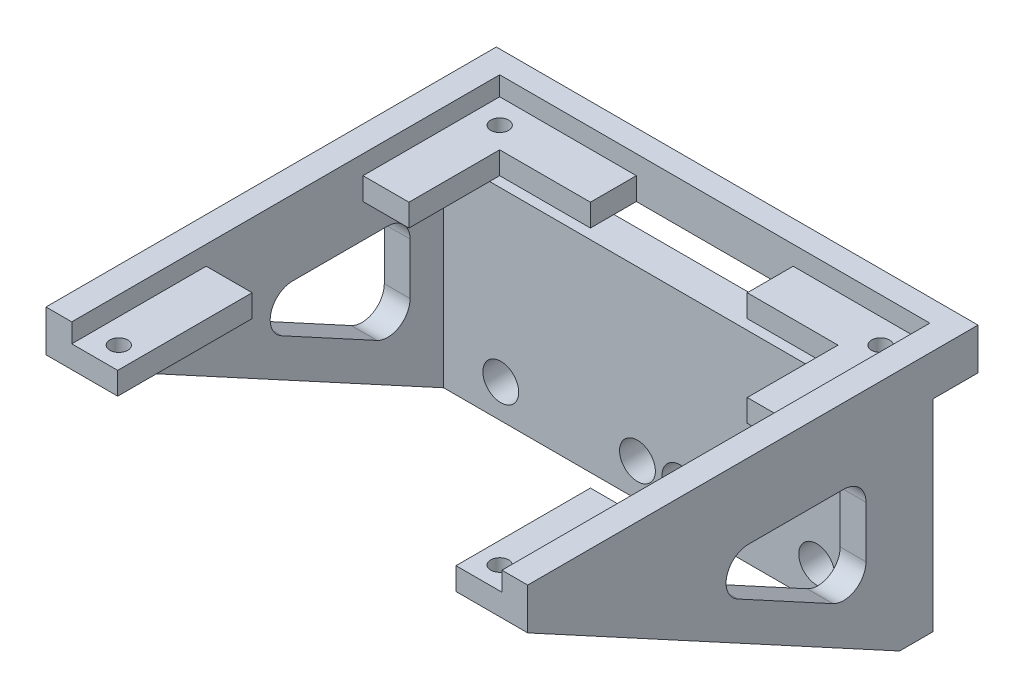
SolidWorks part; units mm, degrees
ref_plane "前视基准面" through (0, 0, 0) normal (0, 0, 1) x (1, 0, 0)
ref_plane "上视基准面" through (0, 0, 0) normal (0, 1, 0) x (1, 0, 0)
ref_plane "右视基准面" through (0, 0, 0) normal (1, 0, 0) x (0, 0, -1)
sketch "Sketch1" plane through (0, 0, 0) normal (0, 1, 0) x (1, 0, 0)
  line L1 (-21.5, -21.5) -> (21.5, -21.5)
  line L2 (-21.5, -21.5) -> (-21.5, 21.5)
  line L3 (-21.5, 21.5) -> (21.5, 21.5)
  line L4 (21.5, -21.5) -> (21.5, 21.5)
  line L5 (-21.5, -21.5) -> (21.5, 21.5) construction
  line L6 (-21.5, 21.5) -> (21.5, -21.5) construction
  point P0 (0, 0)
  dimension "D1" = 43
  dimension "D2" = 43
extrude "Boss-Extrude1" add sketch "Sketch1" along normal blind 24
sketch "Sketch2" plane through (0, 24, 0) normal (0, 1, 0) x (1, 0, 0)
  line L0 (0, 0) -> (0, -21.5) construction
  line L1 (-21.5, -21.5) -> (21.5, -21.5) construction
  line L3 (-19.2, -21.5) -> (19.2, -21.5)
  line L4 (-19.2, -21.5) -> (-19.2, 16.7)
  line L5 (-19.2, 16.7) -> (19.2, 16.7)
  line L6 (19.2, -21.5) -> (19.2, 16.7)
  dimension "D1" = 38.4
  dimension "D2" = 19.2
  dimension "D3" = 38.2
extrude "Cut-Extrude1" cut sketch "Sketch2" against normal blind 1.7
sketch "Sketch3" plane through (0, 22.3, 0) normal (0, 1, 0) x (1, 0, 0)
  line L0 (0, -21.5) -> (0, -2.5) construction
  line L1 (-19.2, -21.5) -> (19.2, -21.5) construction
  line L3 (-17, -19.5) -> (17, -19.5)
  line L4 (-17, -19.5) -> (-17, 14.5)
  line L5 (-17, 14.5) -> (17, 14.5)
  line L6 (17, -19.5) -> (17, 14.5)
  line L7 (-17, -19.5) -> (17, 14.5) construction
  line L8 (-17, 14.5) -> (17, -19.5) construction
  dimension "D1" = 19
  dimension "D2" = 34
  dimension "D3" = 34
hole_wizard "Ø1.6 (1.6) Diameter Hole1" positions "3DSketch1" profile "Sketch4" hole size "Ø1.6" standard "ANSI Metric" end condition through all
sketch3d "3DSketch1"
  point P0 (-17, 22.3, -14.5)
  point P3 (17, 22.3, -14.5)
  point P6 (17, 22.3, 19.5)
  point P9 (-17, 22.3, 19.5)
sketch "Sketch4" plane through (-17, 22.3, -14.5) normal (1, 0, 0) x (0, 0, 1)
  line L0 (0, 0) -> (0, 22.3)
  line L1 (0, 22.3) -> (0.8, 22.3)
  line L2 (0.8, 22.3) -> (0.8, 0)
  line L5 (0.8, 0) -> (0, 0)
  line L11 (0, -6.35) -> (0, 107.95) construction
  dimension "Thru Hole Dia." = 1.6
  dimension "Thru Hole Depth" = 22.3
sketch "Sketch5" plane through (0, 22.3, 0) normal (0, 1, 0) x (1, 0, 0)
  line L0 (-15.1, -21.5) -> (-15.1, 12.6)
  line L1 (-19.2, -21.5) -> (19.2, -21.5) construction
  line L2 (-15.1, 12.6) -> (15.1, 12.6)
  line L3 (15.1, 12.6) -> (15.1, -21.5)
  line L4 (15.1, -21.5) -> (-15.1, -21.5)
  line L5 (0, -21.5) -> (0, -2.5) construction
  dimension "D1" = 15.1
  dimension "D2" = 15.1
  dimension "D3" = 15.1
extrude "Cut-Extrude2" cut sketch "Sketch5" against normal blind 2
sketch "Sketch6" plane through (0, 22.3, 0) normal (0, 1, 0) x (1, 0, 0)
  line L0 (0, 0) -> (0, 16.7) construction
  line L1 (19.2, 16.7) -> (-19.2, 16.7) construction
  line L3 (-7, 16.7) -> (7, 16.7)
  line L4 (-7, 16.7) -> (-7, 4.7)
  line L5 (-7, 4.7) -> (7, 4.7)
  line L6 (7, 16.7) -> (7, 4.7)
  dimension "D1" = 12
  dimension "D2" = 7
  dimension "D3" = 7
extrude "Cut-Extrude3" cut sketch "Sketch6" against normal through all
sketch "Sketch7" plane through (0, 20.3, 0) normal (0, 1, 0) x (1, 0, 0)
  line L0 (-15.1, -21.5) -> (15.1, -21.5) construction
  line L1 (-14.45, -49.4913) -> (14.45, -49.4913)
  line L2 (-14.45, -49.4913) -> (-14.45, 6.4913)
  line L3 (-14.45, 6.4913) -> (14.45, 6.4913)
  line L4 (14.45, -49.4913) -> (14.45, 6.4913)
  line L5 (-14.45, -49.4913) -> (14.45, 6.4913) construction
  line L6 (-14.45, 6.4913) -> (14.45, -49.4913) construction
  point P0 (0, -21.5)
  dimension "D1" = 28.9
extrude "Cut-Extrude4" cut sketch "Sketch7" against normal through all
sketch "Sketch8" plane through (0, 0, 21.5) normal (0, 0, 1) x (1, 0, 0)
  line L1 (-14.45, 20.3) -> (-21.5, 20.3)
  line L2 (-14.45, 20.3) -> (-14.45, 0)
  line L3 (-14.45, 0) -> (-21.5, 0)
  line L4 (-21.5, 20.3) -> (-21.5, 0)
extrude "Boss-Extrude2" add sketch "Sketch8" along normal blind 8.2
mirror "Mirror1" about plane through (0, 0, 0) normal (1, 0, 0) of "Boss-Extrude2"
sketch "Sketch9" plane through (-14.45, 0, 0) normal (1, 0, 0) x (0, 0, -1)
  line L0 (6.4913, 0) -> (6.4913, 20.3) construction
  line L1 (-29.7, 0) -> (6.4913, 0)
  line L2 (-29.7, 0) -> (-29.7, 11.8)
  line L3 (-29.7, 11.8) -> (6.4913, 11.8)
  line L4 (6.4913, 0) -> (6.4913, 11.8)
  line L5 (6.4913, 20.3) -> (-29.7, 20.3) construction
  dimension "D1" = 8.5
extrude "Cut-Extrude5" cut sketch "Sketch9" against normal blind 4.1
mirror "Mirror2" about plane through (0, 0, 0) normal (1, 0, 0) of "Cut-Extrude5"
sketch "Sketch10" plane through (-21.5, 0, 0) normal (-1, 0, 0) x (0, 0, 1)
  line L1 (6.7, 5.05) -> (18.7, 5.05)
  line L5 (29.7, 20.3) -> (21.5, 20.3) construction
  dimension "D2" = 12
  dimension "D3" = 15.25
hole_wizard "Ø2.9 (2.9) Diameter Hole1" positions "Sketch11" profile "Sketch12" hole size "Ø2.9" standard "ANSI Metric" end condition through all
sketch "Sketch11" plane through (-21.5, 0, 0) normal (-1, 0, 0) x (0, 0, 1)
  point P0 (6.7, 5.05)
  point P3 (18.7, 5.05)
sketch "Sketch12" plane through (-21.5, 5.05, 6.7) normal (0, 1, 0) x (0, 0, 1)
  line L0 (0, 0) -> (0, 43)
  line L1 (0, 43) -> (1.45, 43)
  line L2 (1.45, 43) -> (1.45, 0)
  line L5 (1.45, 0) -> (0, 0)
  line L11 (0, -6.35) -> (0, 107.95) construction
  dimension "Thru Hole Dia." = 2.9
  dimension "Thru Hole Depth" = 43
sketch "Sketch13" plane through (0, 0, 0) normal (0, -1, 0) x (1, 0, 0)
  line L0 (21.5, -21.5) -> (-21.5, -21.5) construction
  line L1 (22.5, -36.5087) -> (-22.5, -36.5087)
  line L2 (22.5, -36.5087) -> (22.5, -6.4913)
  line L3 (22.5, -6.4913) -> (-22.5, -6.4913)
  line L4 (-22.5, -36.5087) -> (-22.5, -6.4913)
  line L5 (22.5, -36.5087) -> (-22.5, -6.4913) construction
  line L6 (22.5, -6.4913) -> (-22.5, -36.5087) construction
  line L7 (-7, -6.4913) -> (-18.55, -6.4913) construction
  point P0 (0, -21.5)
  dimension "D1" = 45
extrude "Cut-Extrude6" cut sketch "Sketch13" against normal blind 11.8
sketch "Sketch14" plane through (0, 24, 0) normal (0, 1, 0) x (1, 0, 0)
  circle A0 centre (-19.2, 16.7) radius 0.5
  dimension "D1" = 1
sketch "草图1" plane through (0, 0, 29.7) normal (0, 0, 1) x (1, 0, 0)
  line L0 (-7, 20.3) -> (-14.45, 20.3) construction
  line L1 (-28.0658, 20.3) -> (26.3141, 20.3)
  line L2 (-28.0658, 20.3) -> (-28.0658, -5.4429)
  line L3 (-28.0658, -5.4429) -> (26.3141, -5.4429)
  line L4 (26.3141, 20.3) -> (26.3141, -5.4429)
extrude "切除-拉伸1" cut sketch "草图1" against normal through all
sketch "草图2" plane through (0, 24, 0) normal (0, 1, 0) x (1, 0, 0)
  line L1 (-23.9155, 26.9484) -> (27.254, 26.9484)
  line L2 (-23.9155, 26.9484) -> (-23.9155, 18.7)
  line L3 (-23.9155, 18.7) -> (27.254, 18.7)
  line L4 (27.254, 26.9484) -> (27.254, 18.7)
  line L6 (-7, 16.7) -> (-19.2, 16.7) construction
  dimension "D1" = 2
extrude "切除-拉伸4" cut sketch "草图2" against normal blind 10
sketch "草图3" plane through (0, 20.3, 0) normal (0, -1, 0) x (1, 0, 0)
  line L0 (17, 19.5) -> (17, -14.5) construction
  line L1 (-17, 19.5) -> (-17, -14.5) construction
  line L2 (-19.2, 9.5) -> (19.2, 9.5)
  line L3 (-19.2, 9.5) -> (-19.2, -4.5)
  line L4 (-19.2, -4.5) -> (19.2, -4.5)
  line L5 (19.2, 9.5) -> (19.2, -4.5)
  point P12 (19.5094, 9.5)
  point P13 (17, -4.5)
  point P14 (0, 0)
  point P15 (19.5094, -4.5)
  dimension "D1" = 10
  dimension "D2" = 10
  dimension "D3" = 2.2
  dimension "D4" = 2.2
extrude "切除-拉伸5" cut sketch "草图3" against normal through all
sketch "草图4" plane through (0, 20.3, 0) normal (0, -1, 0) x (1, 0, 0)
  line L0 (-21.5, -18.7) -> (-21.5, 21.5) construction
  line L1 (-21.5, -11.7) -> (21.5, -11.7)
  line L2 (-21.5, -11.7) -> (-21.5, -14.7)
  line L3 (-21.5, -14.7) -> (21.5, -14.7)
  line L4 (21.5, -11.7) -> (21.5, -14.7)
  line L5 (21.5, 21.5) -> (21.5, -18.7) construction
  line L6 (-21.5, -18.7) -> (21.5, -18.7) construction
  dimension "D1" = 3
  dimension "D2" = 4
extrude "凸台-拉伸1" add sketch "草图4" along normal blind 18
sketch "草图5" plane through (0, 0, -14.7) normal (0, 0, -1) x (-1, 0, 0)
  line L0 (7, 20.3) -> (-7, 20.3) construction
  line L1 (-21.5, 2.3) -> (-21.5, 20.3) construction
  line L2 (-7, 20.3) -> (-16.2254, 20.3) construction
  line L3 (21.5, 2.3) -> (21.5, 20.3) construction
  circle A0 centre (0, 14.3) radius 2.75
  circle A1 centre (-1.9, 5.3) radius 1.6
  circle A2 centre (14.1, 5.3) radius 1.6
  dimension "D3" = 5.5
  dimension "D4" = 3.2
  dimension "D7" = 16
  dimension "D1" = 6
  dimension "D2" = 21.5
  dimension "D5" = 15
  dimension "D6" = 7.4
extrude "切除-拉伸6" cut sketch "草图5" against normal through all contours A1 | A2 region at (1.9, 5.3, -14.7)
extrude "凸台-拉伸2" add sketch "草图5<4>" along normal blind 3 contours A0 region at (0, 14.3, -14.7)
sketch "草图5<4>" plane through (0, 0, -14.7) normal (0, 0, -1) x (-1, 0, 0) same geometry as "草图5"
fillet "圆角1" radius 1 1 edges at (-2.75, 14.3, -17.7)
sketch "草图6" plane through (21.5, 0, 0) normal (1, 0, 0) x (0, 0, -1)
  line L0 (-21.5, 20.3) -> (11.7, 2.3)
  line L1 (11.7, 2.3) -> (11.7, 20.3)
  line L2 (11.7, 20.3) -> (-21.5, 20.3)
  line L3 (-9.6724, 17.3) -> (8.7, 7.3391)
  line L4 (8.7, 7.3391) -> (8.7, 17.3)
  line L5 (8.7, 17.3) -> (-9.6724, 17.3)
  dimension "D1" = 3
extrude "凸台-拉伸3" add sketch "草图6" against normal up to surface (2.3 mm away) up to face at (19.2, 22.225, 2.45)
mirror "镜向1" about plane through (0, 0, 0) normal (1, 0, 0) of "切除-拉伸6"
sketch "草图7" plane through (-21.5, 0, 0) normal (-1, 0, 0) x (0, 0, 1)
  line L0 (-11.7, 2.3) -> (-11.7, 20.3)
  line L1 (-11.7, 20.3) -> (21.5, 20.3)
  line L2 (21.5, 20.3) -> (-11.7, 2.3)
  line L3 (-8.7, 17.3) -> (9.6724, 17.3)
  line L4 (9.6724, 17.3) -> (-8.7, 7.3391)
  line L5 (-8.7, 7.3391) -> (-8.7, 17.3)
  dimension "D1" = 3
extrude "凸台-拉伸4" add sketch "草图7" against normal up to surface (2.3 mm away) up to face at (-19.2, 22.225, 2.45)
fillet "圆角2" radius 2 6 edges at (-20.35, 17.3, 9.6724) (-20.35, 17.3, -8.7) (-20.35, 7.3391, -8.7) (20.35, 17.3, -8.7) (20.35, 7.3391, -8.7) (20.35, 17.3, 9.6724)
